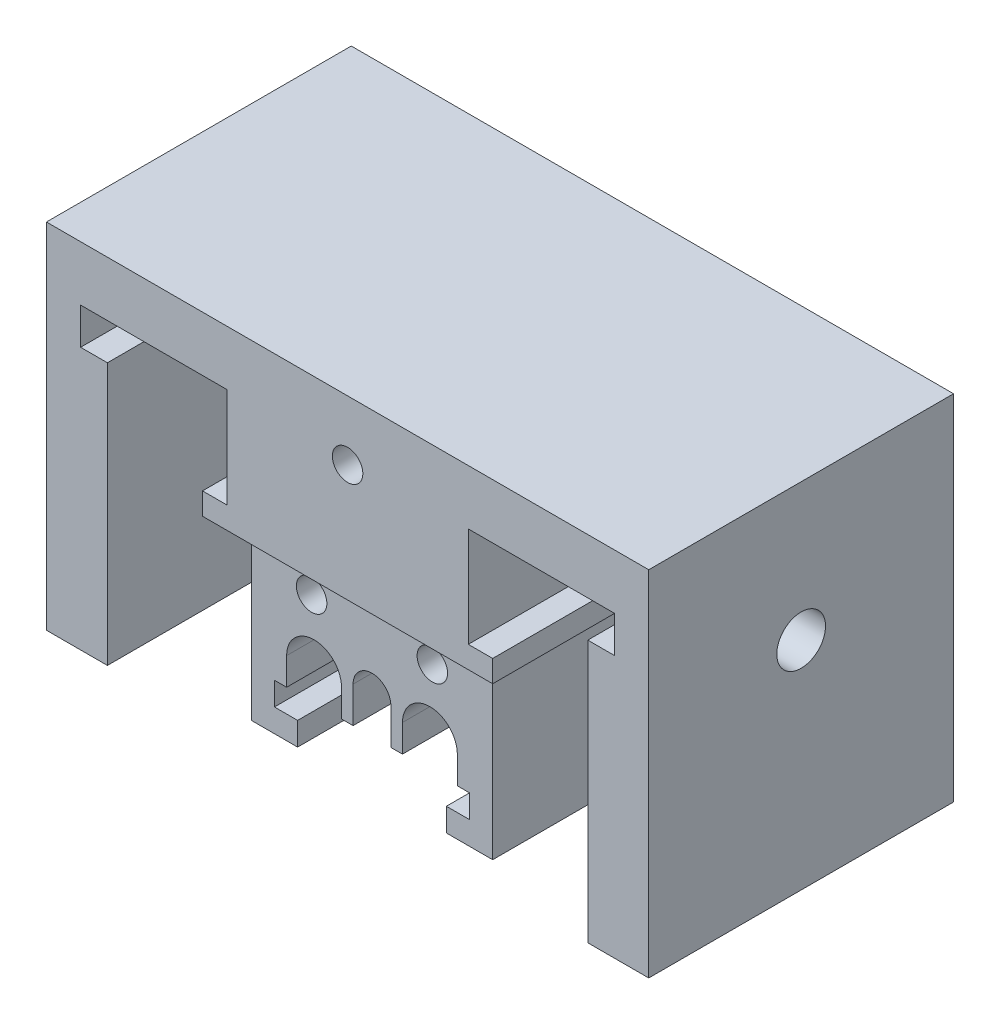
SolidWorks part; units mm, degrees
ref_plane "Front Plane" through (0, 0, 0) normal (0, 0, 1) x (1, 0, 0)
ref_plane "Top Plane" through (0, 0, 0) normal (0, 1, 0) x (1, 0, 0)
ref_plane "Right Plane" through (0, 0, 0) normal (1, 0, 0) x (0, 0, -1)
sketch "Sketch1" plane through (0, 0, 0) normal (0, 0, 1) x (1, 0, 0)
  line L0 (-21.9, 7) -> (-21.9, 10)
  line L1 (-21.9, 10) -> (-9.9, 10)
  line L2 (-9.9, 10) -> (-9.9, 1.8)
  line L3 (-9.9, -14.5) -> (9.9, -14.5)
  line L4 (9.9, -14.5) -> (9.9, 0)
  line L5 (9.9, 10) -> (21.9, 10)
  line L6 (21.9, 10) -> (21.9, 7)
  line L7 (19.7, -14.5) -> (24.7, -14.5)
  line L8 (24.7, -14.5) -> (24.7, 14.5)
  line L9 (24.7, 14.5) -> (-24.7, 14.5)
  line L14 (-24.7, 14.5) -> (-24.7, -14.5)
  line L16 (-21.9, 7) -> (-19.7, 7)
  line L17 (-19.7, 7) -> (-19.7, -14.5)
  line L18 (-19.7, -14.5) -> (-24.7, -14.5)
  line L19 (21.9, 7) -> (19.7, 7)
  line L20 (19.7, 7) -> (19.7, -14.5)
  line L22 (-9.9, 1.8) -> (-11.9, 1.8)
  line L23 (-11.9, 1.8) -> (-11.9, 0)
  line L24 (-11.9, 0) -> (-9.9, 0)
  line L25 (9.9, 1.8) -> (11.9, 1.8)
  line L26 (11.9, 1.8) -> (11.9, 0)
  line L27 (11.9, 0) -> (9.9, 0)
  line L28 (-9.9, 0) -> (-9.9, -14.5)
  line L29 (9.9, 1.8) -> (9.9, 10)
  point P0 (10.8386, -8.0172)
  point P9 (-24.7, 0)
  point P25 (0, 0)
  point P29 (0, -14.5)
  dimension "D1" = 19.8
  dimension "D2" = 12
  dimension "D3" = 4.5
  dimension "D4" = 4.5
  dimension "D5" = 24.5
  dimension "D6" = 5
  dimension "D7" = 2.2
  dimension "D8" = 1.8
  dimension "D9" = 14.5
  dimension "D10" = 3
  dimension "D11" = 2
extrude "Boss-Extrude1" add sketch "Sketch1" along normal blind 25
sketch "Sketch2" plane through (-24.7, 0, 0) normal (-1, 0, 0) x (0, 0, 1)
  line L0 (25, 1.8) -> (0, 1.8) construction
  line L2 (25, 1.8) -> (0, 1.8) construction
  line L3 (9.1108, 1.25) -> (17.7065, 1.25) construction
  circle A0 centre (12.5, 3.25) radius 2
  point P2 (12.5, 3.4648)
  point P3 (12.5, 1.8)
  dimension "D1" = 4
  dimension "D2" = 0.55
extrude "Cut-Extrude1" cut sketch "Sketch2" against normal through all
sketch "Sketch5" plane through (0, 0, 0) normal (1, 0, 0) x (0, 0, -1)
  line L1 (-8.4008, 3.25) -> (-10.4504, 6.8)
  line L2 (-10.4504, 6.8) -> (-14.5496, 6.8)
  line L3 (-14.5496, 6.8) -> (-16.5992, 3.25)
  line L4 (-16.5992, 3.25) -> (-14.5496, -0.3)
  line L5 (-14.5496, -0.3) -> (-10.4504, -0.3)
  line L6 (-10.4504, -0.3) -> (-8.4008, 3.25)
  circle A2 centre (-12.5, 3.25) radius 3.55 construction
  point P1 (-13.4252, 5.954)
  dimension "D1" = 7.1
extrude "Cut-Extrude2" cut sketch "Sketch5" against normal blind 6 and the other way blind 6
sketch "Sketch6" plane through (0, 0, 0) normal (0, 0, 1) x (1, 0, 0)
  line L0 (6, 6.8) -> (-6, 6.8) construction
  line L1 (3, 6.8) -> (-3, 6.8)
  line L2 (3, 6.8) -> (3, -0.3)
  line L3 (3, -0.3) -> (-3, -0.3)
  line L4 (-3, 6.8) -> (-3, -0.3)
  line L5 (6, -0.3) -> (-6, -0.3) construction
  point P9 (0, -0.3)
  dimension "D1" = 6
extrude "Cut-Extrude3" cut sketch "Sketch6" along normal up to vertex (10.4504 mm away) up to point (-6, -0.3, 10.4504)
sketch "Sketch9" plane through (0, 0, 25) normal (0, 0, 1) x (1, 0, 0)
  line L2 (-6.1, -14.5) -> (6.1, -14.5)
  line L4 (-9.9, -14.5) -> (9.9, -14.5) construction
  line L5 (6.1, -14.5) -> (6.1, -12.6)
  line L6 (6.1, -12.6) -> (8, -12.6)
  line L7 (8, -12.6) -> (8, -10.7)
  line L8 (8, -10.7) -> (-8, -10.7)
  line L9 (-8, -10.7) -> (-8, -12.6)
  line L10 (-8, -12.6) -> (-6.1, -12.6)
  line L11 (-6.1, -12.6) -> (-6.1, -14.5)
  line L12 (-9.9, 0) -> (-9.9, -14.5) construction
  line L14 (-9.9, -12.6) -> (-8, -12.6) construction
  point P12 (0, -10.7)
  dimension "D1" = 1.9
extrude "Cut-Extrude4" cut sketch "Sketch9" against normal up to next
sketch "Sketch11" plane through (0, 0, 25) normal (0, 0, 1) x (1, 0, 0)
  line L0 (-8, -10.7) -> (-8, -12.6) construction
  line L2 (8, -12.6) -> (8, -10.7) construction
  line L3 (-7, -8.45) -> (-7, -10.7)
  line L4 (-2.5, -8.45) -> (-2.5, -10.7)
  line L5 (2.5, -8.45) -> (2.5, -10.7)
  line L6 (7, -8.45) -> (7, -10.7)
  line L7 (-7, -10.7) -> (-2.5, -10.7)
  line L8 (2.5, -10.7) -> (7, -10.7)
  line L9 (-4.75, -8.45) -> (-4.75, -6.2) construction
  line L10 (8, -10.7) -> (-8, -10.7) construction
  line L12 (-1.55, -7.75) -> (-1.55, -10.7)
  line L13 (-1.55, -10.7) -> (1.55, -10.7)
  line L14 (1.55, -7.75) -> (1.55, -10.7)
  arc A0 (-2.5, -8.45) -> (-7, -8.45) centre (-4.75, -8.45) ccw
  arc A1 (7, -8.45) -> (2.5, -8.45) centre (4.75, -8.45) ccw
  arc A2 (-1.55, -7.75) -> (1.55, -7.75) centre (0, -7.75) cw
  point P4 (0, 0)
  point P22 (0, -6.2)
  point P23 (4.75, -6.2)
  point P25 (0, 0)
  dimension "D1" = 4.5
  dimension "D2" = 1
  dimension "D3" = 1
  dimension "D4" = 3.1
extrude "Cut-Extrude5" cut sketch "Sketch11" against normal blind 23
sketch "Sketch12" plane through (0, 0, 25) normal (0, 0, 1) x (1, 0, 0)
  line L0 (6.1, -14.5) -> (9.9, -14.5) construction
  line L1 (-9.9, 0) -> (9.9, 0)
  line L2 (-9.9, 0) -> (-9.9, -14.5)
  line L3 (-9.9, -14.5) -> (9.9, -14.5)
  line L4 (9.9, 0) -> (9.9, -14.5)
  line L5 (-9.9, 0) -> (9.9, -14.5) construction
  line L6 (-9.9, -14.5) -> (9.9, 0) construction
  line L7 (-9.9, 0) -> (-9.9, -14.5) construction
  line L8 (9.9, -14.5) -> (9.9, 0) construction
  line L9 (9.9, 0) -> (11.9, 0) construction
  point P0 (0, -7.25)
extrude "Cut-Extrude6" cut sketch "Sketch12" against normal blind 2
sketch "Sketch13" plane through (0, 0, 23) normal (0, 0, 1) x (1, 0, 0)
  line L0 (0, 0) -> (0, -6.2) construction
  line L1 (9.9, 0) -> (-9.9, 0) construction
  line L2 (-9.9, -3.1) -> (0, -3.1) construction
  line L5 (-9.9, 0) -> (-9.9, -14.5) construction
  line L6 (0, -3.1) -> (9.9, -3.1) construction
  line L7 (9.9, -14.5) -> (9.9, 0) construction
  line L9 (6, 6.8) -> (-6, 6.8) construction
  line L10 (6, 6.8) -> (-6, 6.8) construction
  line L11 (6, -0.3) -> (-6, -0.3) construction
  line L12 (6, -0.3) -> (-6, -0.3) construction
  line L13 (-4.95, -3.1) -> (-4.95, -0.3) construction
  line L14 (0, 9.6) -> (0, 6.8) construction
  circle A0 centre (-4.95, -3.1) radius 1.25
  circle A1 centre (4.95, -3.1) radius 1.25
  arc A2 (1.55, -7.75) -> (-1.55, -7.75) centre (0, -7.75) ccw construction
  circle A3 centre (0, 9.6) radius 1.25
  point P15 (0, -3.1)
  point P19 (0, 9.6)
  point P20 (-4.95, -3.1)
  point P21 (4.95, -3.1)
  dimension "D1" = 2.5
extrude "Cut-Extrude7" cut sketch "Sketch13" against normal blind 12 and the other way blind 2
